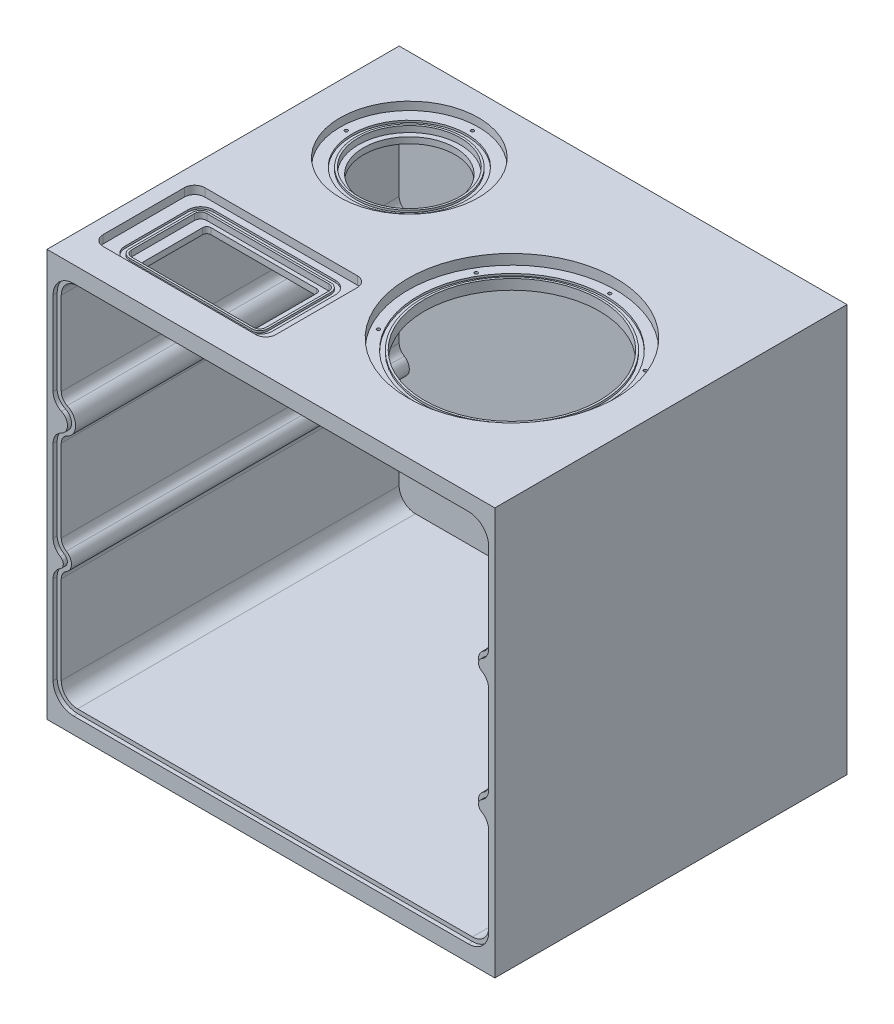
SolidWorks part; units mm, degrees
material "6061 Alloy"
ref_plane "Front Plane" through (0, 0, 0) normal (0, 0, 1) x (1, 0, 0)
ref_plane "Top Plane" through (0, 0, 0) normal (0, 1, 0) x (1, 0, 0)
ref_plane "Right Plane" through (0, 0, 0) normal (1, 0, 0) x (0, 0, -1)
sketch "Sketch1" plane through (0, 0, 0) normal (0, 0, 1) x (1, 0, 0)
  line L0 (0, 100) -> (0, -100) construction
  line L1 (-110, 100) -> (110, 100)
  line L2 (-110, 100) -> (-110, -100)
  line L3 (-110, -100) -> (110, -100)
  line L4 (110, 100) -> (110, -100)
  line L5 (-105, 22.9298) -> (-105, -25)
  line L6 (-105, -35) -> (-105, -90)
  line L7 (-105, 90) -> (105, 90)
  line L8 (-105, 90) -> (-105, 37.0702)
  line L9 (-105, -90) -> (105, -90)
  line L10 (105, 90) -> (105, 35)
  line L11 (105, 25) -> (105, -25)
  line L12 (105, -35) -> (105, -90)
  arc A1 (-105, 22.9298) -> (-105, 37.0702) centre (-105, 30) ccw
  arc A4 (-105, -35) -> (-105, -25) centre (-105, -30) ccw
  arc A6 (105, 35) -> (105, 25) centre (105, 30) ccw
  arc A7 (105, -25) -> (105, -35) centre (105, -30) ccw
  point P0 (0, 0)
  point P6 (0, 0)
  dimension "D9" = 60
  dimension "D10" = 60
  dimension "D1" = 220
  dimension "D2" = 200
  dimension "D3" = 210
  dimension "D4" = 180
  dimension "D5" = 90
  dimension "D6" = 105
  dimension "D8" = 100
  dimension "D12" = 5
  dimension "D13" = 60
  dimension "D14" = 60
extrude "Boss-Extrude1" add sketch "Sketch1" along normal blind 5 contours L2 L3 L4 L1
extrude "Boss-Extrude2" add sketch "Sketch1<3>" along normal blind 173
sketch "Sketch1<3>" plane through (0, 0, 0) normal (0, 0, 1) x (1, 0, 0) same geometry as "Sketch1"
fillet "Fillet1" radius 8 4 edges at (105, -90, 89) (-105, -90, 89) (105, 90, 89) (-105, 90, 89)
fillet "Fillet2" radius 5 8 edges at (105, -35, 89) (105, -25, 89) (105, 35, 89) (105, 25, 89) (-105, 37.0702, 89) (-105, 22.9298, 89) (-105, -25, 89) (-105, -35, 89)
sketch "Sketch2" plane through (0, 0, 173) normal (0, 0, 1) x (1, 0, 0)
  line L0 (107, -82) -> (107, -38.6603)
  line L1 (107, -21.3397) -> (107, 21.3397)
  line L2 (107, 38.6603) -> (107, 82)
  line L3 (97, 92) -> (-97, 92)
  line L4 (-107, 82) -> (-107, 40.9858)
  line L5 (-107, 19.0142) -> (-107, -21.3397)
  line L6 (-107, -38.6603) -> (-107, -82)
  line L7 (-97, -92) -> (97, -92)
  line L8 (105, -82) -> (105, -38.6603)
  line L9 (105, -21.3397) -> (105, 21.3397)
  line L10 (105, 38.6603) -> (105, 82)
  line L11 (97, 90) -> (-97, 90)
  line L12 (-105, 82) -> (-105, 40.9858)
  line L13 (-105, 19.0142) -> (-105, -21.3397)
  line L14 (-105, -38.6603) -> (-105, -82)
  line L15 (-97, -90) -> (97, -90)
  line L16 (105, -82) -> (105, -38.6603)
  line L17 (105, -21.3397) -> (105, 21.3397)
  line L18 (105, 38.6603) -> (105, 82)
  line L19 (97, 90) -> (-97, 90)
  line L20 (-105, 82) -> (-105, 40.9858)
  line L21 (-105, 19.0142) -> (-105, -21.3397)
  line L22 (-105, -38.6603) -> (-105, -82)
  line L23 (-97, -90) -> (97, -90)
  arc A0 (107, -38.6603) -> (103.5, -32.5981) centre (100, -38.6603) ccw
  arc A1 (103.5, -27.4019) -> (103.5, -32.5981) centre (105, -30) ccw
  arc A2 (103.5, -27.4019) -> (107, -21.3397) centre (100, -21.3397) ccw
  arc A3 (107, 21.3397) -> (103.5, 27.4019) centre (100, 21.3397) ccw
  arc A4 (103.5, 32.5981) -> (103.5, 27.4019) centre (105, 30) ccw
  arc A5 (103.5, 32.5981) -> (107, 38.6603) centre (100, 38.6603) ccw
  arc A6 (107, 82) -> (97, 92) centre (97, 82) ccw
  arc A7 (-97, 92) -> (-107, 82) centre (-97, 82) ccw
  arc A8 (-107, 40.9858) -> (-102.8997, 34.6147) centre (-100, 40.9858) ccw
  arc A9 (-102.8997, 25.3853) -> (-102.8997, 34.6147) centre (-105, 30) ccw
  arc A10 (-102.8997, 25.3853) -> (-107, 19.0142) centre (-100, 19.0142) ccw
  arc A11 (-107, -21.3397) -> (-103.5, -27.4019) centre (-100, -21.3397) ccw
  arc A12 (-103.5, -32.5981) -> (-103.5, -27.4019) centre (-105, -30) ccw
  arc A13 (-103.5, -32.5981) -> (-107, -38.6603) centre (-100, -38.6603) ccw
  arc A14 (-107, -82) -> (-97, -92) centre (-97, -82) ccw
  arc A15 (97, -92) -> (107, -82) centre (97, -82) ccw
  arc A16 (105, -38.6603) -> (102.5, -34.3301) centre (100, -38.6603) ccw
  arc A17 (102.5, -25.6699) -> (102.5, -34.3301) centre (105, -30) ccw
  arc A18 (102.5, -25.6699) -> (105, -21.3397) centre (100, -21.3397) ccw
  arc A19 (105, 21.3397) -> (102.5, 25.6699) centre (100, 21.3397) ccw
  arc A20 (102.5, 34.3301) -> (102.5, 25.6699) centre (105, 30) ccw
  arc A21 (102.5, 34.3301) -> (105, 38.6603) centre (100, 38.6603) ccw
  arc A22 (105, 82) -> (97, 90) centre (97, 82) ccw
  arc A23 (-97, 90) -> (-105, 82) centre (-97, 82) ccw
  arc A24 (-105, 40.9858) -> (-102.0712, 36.435) centre (-100, 40.9858) ccw
  arc A25 (-102.0712, 23.565) -> (-102.0712, 36.435) centre (-105, 30) ccw
  arc A26 (-102.0712, 23.565) -> (-105, 19.0142) centre (-100, 19.0142) ccw
  arc A27 (-105, -21.3397) -> (-102.5, -25.6699) centre (-100, -21.3397) ccw
  arc A28 (-102.5, -34.3301) -> (-102.5, -25.6699) centre (-105, -30) ccw
  arc A29 (-102.5, -34.3301) -> (-105, -38.6603) centre (-100, -38.6603) ccw
  arc A30 (-105, -82) -> (-97, -90) centre (-97, -82) ccw
  arc A31 (97, -90) -> (105, -82) centre (97, -82) ccw
  arc A32 (105, -38.6603) -> (102.5, -34.3301) centre (100, -38.6603) ccw
  arc A33 (102.5, -25.6699) -> (102.5, -34.3301) centre (105, -30) ccw
  arc A34 (102.5, -25.6699) -> (105, -21.3397) centre (100, -21.3397) ccw
  arc A35 (105, 21.3397) -> (102.5, 25.6699) centre (100, 21.3397) ccw
  arc A36 (102.5, 34.3301) -> (102.5, 25.6699) centre (105, 30) ccw
  arc A37 (102.5, 34.3301) -> (105, 38.6603) centre (100, 38.6603) ccw
  arc A38 (105, 82) -> (97, 90) centre (97, 82) ccw
  arc A39 (-97, 90) -> (-105, 82) centre (-97, 82) ccw
  arc A40 (-105, 40.9858) -> (-102.0712, 36.435) centre (-100, 40.9858) ccw
  arc A41 (-102.0712, 23.565) -> (-102.0712, 36.435) centre (-105, 30) ccw
  arc A42 (-102.0712, 23.565) -> (-105, 19.0142) centre (-100, 19.0142) ccw
  arc A43 (-105, -21.3397) -> (-102.5, -25.6699) centre (-100, -21.3397) ccw
  arc A44 (-102.5, -34.3301) -> (-102.5, -25.6699) centre (-105, -30) ccw
  arc A45 (-102.5, -34.3301) -> (-105, -38.6603) centre (-100, -38.6603) ccw
  arc A46 (-105, -82) -> (-97, -90) centre (-97, -82) ccw
  arc A47 (97, -90) -> (105, -82) centre (97, -82) ccw
  dimension "D1" = 0
  dimension "D2" = 2
sketch "Sketch4" plane through (0, 100, 0) normal (0, 1, 0) x (1, 0, 0)
  line L0 (110, -173) -> (110, 0) construction
  line L1 (110, -173) -> (-110, -173) construction
  circle A0 centre (42, -96.6) radius 43
  circle A1 centre (42, -96.6) radius 44
  circle A2 centre (42, -96.6) radius 46
  circle A3 centre (42, -96.6) radius 51
  dimension "D2" = 76.4
  dimension "D3" = 86
  dimension "D4" = 88
  dimension "D5" = 92
  dimension "D6" = 102
  dimension "D1" = 68
extrude "Cut-Extrude3" cut sketch "Sketch4" against normal blind 10 contours A0
extrude "Cut-Extrude4" cut sketch "Sketch4<3>" against normal blind 5 contours A3
sketch "Sketch4<3>" plane through (0, 100, 0) normal (0, 1, 0) x (1, 0, 0) same geometry as "Sketch4"
extrude "Cut-Extrude6" cut sketch "Sketch4<5>" against normal blind 6 contours A2 A1 region at (-2.6989, 100, 96.6)
sketch "Sketch4<5>" plane through (0, 100, 0) normal (0, 1, 0) x (1, 0, 0) same geometry as "Sketch4"
extrude "Cut-Extrude9" cut sketch "Sketch2" against normal blind 2
sketch "Sketch5" plane through (0, 95, 0) normal (0, 1, 0) x (1, 0, 0)
  line L0 (42, -96.6) -> (42, 9.4616) construction
  circle A0 centre (42, -48.6) radius 0.7835
  circle A6 centre (83.5692, -72.6) radius 0.7835
  circle A7 centre (83.5692, -120.6) radius 0.7835
  circle A8 centre (42, -144.6) radius 0.7835
  circle A9 centre (0.4308, -120.6) radius 0.7835
  circle A10 centre (0.4308, -72.6) radius 0.7835
  point P18 (44.5, -92.2699)
  point P19 (42, -96.6)
  dimension "D1" = 1.567
  dimension "D2" = 48
  dimension "D3" = 6
extrude "Cut-Extrude7" cut sketch "Sketch5" against normal blind 4
sketch "Sketch6" plane through (0, 100, 0) normal (0, 1, 0) x (1, 0, 0)
  line L0 (-110, -173) -> (-110, 0) construction
  line L1 (-88, -116.5) -> (-32, -116.5)
  line L2 (-88, -116.5) -> (-88, -149.5)
  line L3 (-88, -149.5) -> (-32, -149.5)
  line L4 (-32, -116.5) -> (-32, -149.5)
  line L5 (-88, -116.5) -> (-32, -149.5) construction
  line L6 (-88, -149.5) -> (-32, -116.5) construction
  line L7 (110, -173) -> (-110, -173) construction
  line L9 (-93, -114.5) -> (-27, -114.5)
  line L10 (-93, -114.5) -> (-93, -151.5)
  line L11 (-93, -151.5) -> (-27, -151.5)
  line L12 (-27, -114.5) -> (-27, -151.5)
  line L13 (-93, -114.5) -> (-27, -151.5) construction
  line L14 (-93, -151.5) -> (-27, -114.5) construction
  line L19 (-94, -113.5) -> (-26, -113.5)
  line L20 (-26, -113.5) -> (-26, -152.5)
  line L24 (-94, -152.5) -> (-26, -152.5)
  line L25 (-94, -113.5) -> (-94, -152.5)
  line L26 (-96.2, -111.3) -> (-23.8, -111.3)
  line L27 (-23.8, -111.3) -> (-23.8, -154.7)
  line L28 (-96.2, -154.7) -> (-23.8, -154.7)
  line L29 (-96.2, -111.3) -> (-96.2, -154.7)
  line L31 (-102.5, -108) -> (-17.5, -108)
  line L32 (-102.5, -108) -> (-102.5, -158)
  line L33 (-102.5, -158) -> (-17.5, -158)
  line L34 (-17.5, -108) -> (-17.5, -158)
  line L35 (-102.5, -108) -> (-17.5, -158) construction
  line L36 (-102.5, -158) -> (-17.5, -108) construction
  point P0 (-60, -133)
  point P9 (-60, -133)
  point P14 (-60, -133)
  point P23 (-60, -133)
  dimension "D1" = 50
  dimension "D2" = 40
  dimension "D3" = 56
  dimension "D4" = 33
  dimension "D5" = 66
  dimension "D6" = 37
  dimension "D7" = 1
  dimension "D8" = 2.2
  dimension "D9" = 85
  dimension "D10" = 50
extrude "Cut-Extrude8" cut sketch "Sketch6" against normal blind 10 contours L4 L1 L2 L3 region at (-60, 100, 133)
extrude "Cut-Extrude10" cut sketch "Sketch6<3>" against normal blind 4 contours L32 L33 L34 L31
sketch "Sketch6<3>" plane through (0, 100, 0) normal (0, 1, 0) x (1, 0, 0) same geometry as "Sketch6"
extrude "Cut-Extrude11" cut sketch "Sketch6<4>" against normal blind 7 contours L12 L9 L10 L11 L1 L4 L3 L2 region at (-60, 100, 115.2566)
sketch "Sketch6<4>" plane through (0, 100, 0) normal (0, 1, 0) x (1, 0, 0) same geometry as "Sketch6"
extrude "Cut-Extrude12" cut sketch "Sketch6<5>" against normal blind 5 contours L26 L29 L28 L27 L25 L19 L20 L24 region at (-60, 100, 112.1441)
sketch "Sketch6<5>" plane through (0, 100, 0) normal (0, 1, 0) x (1, 0, 0) same geometry as "Sketch6"
fillet "Fillet3" radius 2 4 edges at (-32, 91.5, 149.5) (-88, 91.5, 149.5) (-32, 91.5, 116.5) (-88, 91.5, 116.5)
fillet "Fillet4" radius 3 4 edges at (-27, 94.5, 151.5) (-93, 94.5, 151.5) (-27, 94.5, 114.5) (-93, 94.5, 114.5)
fillet "Fillet5" radius 4 4 edges at (-26, 95.5, 152.5) (-26, 95.5, 113.5) (-94, 95.5, 152.5) (-94, 95.5, 113.5)
fillet "Fillet6" radius 6.2 4 edges at (-23.8, 95.5, 154.7) (-96.2, 95.5, 154.7) (-23.8, 95.5, 111.3) (-96.2, 95.5, 111.3)
fillet "Fillet7" radius 5 4 edges at (-17.5, 98, 158) (-102.5, 98, 158) (-17.5, 98, 108) (-102.5, 98, 108)
sketch "Sketch7" plane through (0, 100, 0) normal (0, 1, 0) x (1, 0, 0)
  line L0 (-110, -173) -> (-110, 0) construction
  line L1 (110, -173) -> (-110, -173) construction
  circle A0 centre (-60, -45) radius 22.5
  circle A1 centre (-60, -45) radius 25
  circle A2 centre (-60, -45) radius 26
  circle A3 centre (-60, -45) radius 28.2
  circle A4 centre (-60, -45) radius 34
  dimension "D3" = 45
  dimension "D4" = 50
  dimension "D5" = 52
  dimension "D6" = 56.4
  dimension "D7" = 68
  dimension "D1" = 50
  dimension "D2" = 128
extrude "Cut-Extrude13" cut sketch "Sketch7" against normal blind 10 contours A0 region at (-60, 100, 45)
extrude "Cut-Extrude14" cut sketch "Sketch7<3>" against normal blind 7 contours A1 A0 region at (-84.2929, 100, 45)
sketch "Sketch7<3>" plane through (0, 100, 0) normal (0, 1, 0) x (1, 0, 0) same geometry as "Sketch7"
extrude "Cut-Extrude15" cut sketch "Sketch7<4>" against normal blind 4 contours A4 A3 | A2 A1 region at (-85.2646, 100, 45) region at (-93.0383, 100, 45)
sketch "Sketch7<4>" plane through (0, 100, 0) normal (0, 1, 0) x (1, 0, 0) same geometry as "Sketch7"
extrude "Cut-Extrude16" cut sketch "Sketch7<5>" against normal blind 5 contours A3 A2 region at (-87.4024, 100, 45)
sketch "Sketch7<5>" plane through (0, 100, 0) normal (0, 1, 0) x (1, 0, 0) same geometry as "Sketch7"
sketch "Sketch8" plane through (0, 96, 0) normal (0, 1, 0) x (1, 0, 0)
  line L0 (-60, -45) -> (-60, -5.7108) construction
  circle A0 centre (-60, -14) radius 0.7835
  circle A1 centre (-29, -45) radius 0.7835
  circle A2 centre (-60, -76) radius 0.7835
  circle A3 centre (-91, -45) radius 0.7835
  point P14 (-60, -45)
  dimension "D1" = 1.567
  dimension "D2" = 31
  dimension "D3" = 4
extrude "Cut-Extrude17" cut sketch "Sketch8" against normal blind 5
